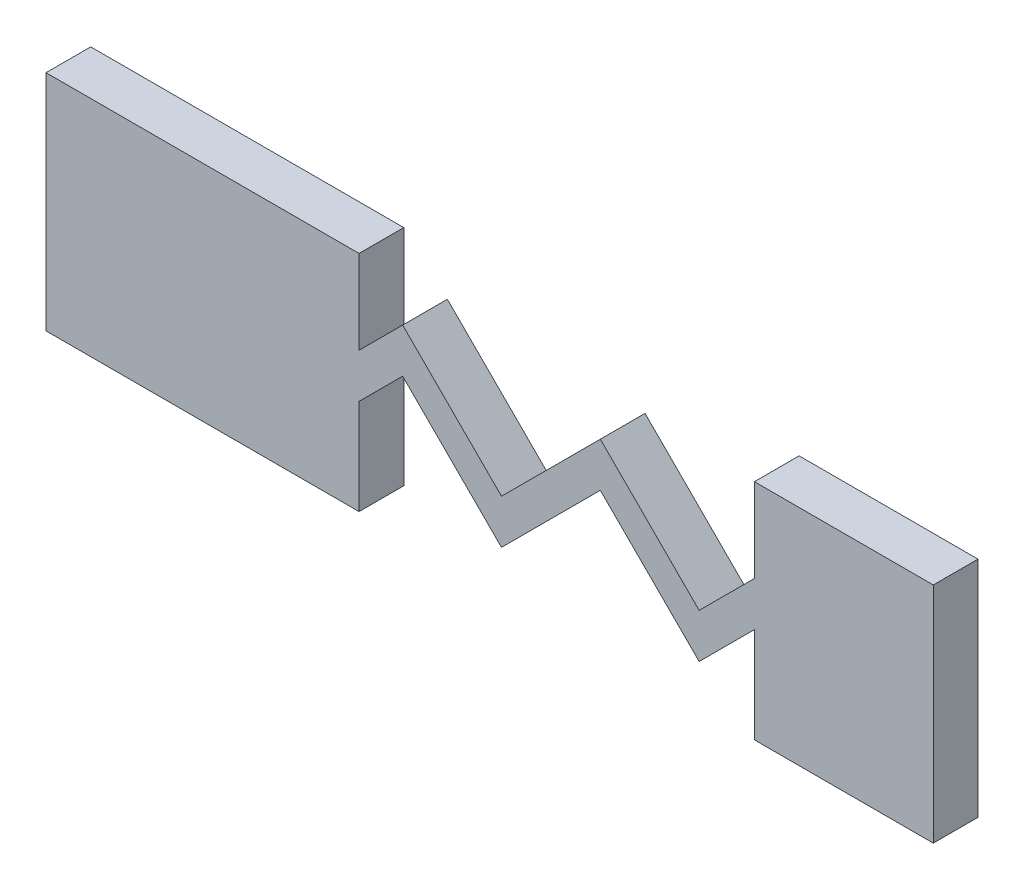
SolidWorks part; units mm, degrees
ref_plane "Front Plane" through (0, 0, 0) normal (0, 0, 1) x (1, 0, 0)
ref_plane "Top Plane" through (0, 0, 0) normal (0, 1, 0) x (1, 0, 0)
ref_plane "Right Plane" through (0, 0, 0) normal (1, 0, 0) x (0, 0, -1)
sketch "Sketch1" plane through (0, 0, 0) normal (0, 0, 1) x (1, 0, 0)
  line L0 (14, 6.25) -> (15.95, 8.2)
  line L1 (0, 0) -> (14, 0)
  line L2 (0, 0) -> (0, 10)
  line L3 (0, 10) -> (14, 10)
  line L4 (14, 0) -> (14, 10)
  line L5 (14, 6.25) -> (14, 4.2701)
  line L6 (15.95, 8.2) -> (15.95, 6.2201)
  line L7 (14, 4.2701) -> (15.95, 6.2201)
  line L9 (15.95, 8.2) -> (15.95, 6.2201)
  line L24 (14, 10) -> (-49986, 10) construction
  line L25 (15.95, 6.2201) -> (20.3701, 1.8)
  line L26 (15.95, 6.2201) -> (15.95, 8.2)
  line L31 (20.3701, 1.8) -> (20.3701, 3.7799)
  line L32 (15.95, 8.2) -> (20.3701, 3.7799)
  line L33 (15.95, 8.2) -> (-49984.05, 8.2) construction
  line L34 (20.3701, 1.8) -> (-49979.6299, 1.8) construction
  line L35 (20.3701, 3.7799) -> (15.95, 8.2)
  line L36 (20.3701, 3.7799) -> (20.3701, 1.8)
  line L37 (15.95, 8.2) -> (15.95, 6.2201)
  line L38 (20.3701, 1.8) -> (15.95, 6.2201)
  line L39 (20.3701, 3.7799) -> (24.7902, 8.2)
  line L40 (20.3701, 3.7799) -> (20.3701, 1.8)
  line L41 (24.7902, 8.2) -> (24.7902, 6.2201)
  line L42 (20.3701, 1.8) -> (24.7902, 6.2201)
  line L43 (24.7902, 6.2201) -> (29.2103, 1.8)
  line L44 (24.7902, 6.2201) -> (24.7902, 8.2)
  line L45 (29.2103, 1.8) -> (29.2103, 3.7799)
  line L46 (24.7902, 8.2) -> (29.2103, 3.7799)
  line L47 (29.2103, 3.7799) -> (31.6804, 6.25)
  line L48 (29.2103, 3.7799) -> (29.2103, 1.8)
  line L49 (31.6804, 6.25) -> (31.6804, 4.2701)
  line L50 (29.2103, 1.8) -> (31.6804, 4.2701)
  line L51 (14, 6.25) -> (-49986, 6.25) construction
  line L52 (14, 10) -> (-49986, 10) construction
  line L53 (14.8952, 0) -> (-49985.1048, 0) construction
  line L54 (31.6804, 6.137) -> (31.6804, -49993.863) construction
  line L56 (31.6804, 10) -> (39.6804, 10)
  line L57 (31.6804, 10) -> (31.6804, 0)
  line L58 (31.6804, 0) -> (39.6804, 0)
  line L59 (39.6804, 10) -> (39.6804, 0)
  dimension "D1" = 10
  dimension "D2" = 14
  dimension "D3" = 45
  dimension "D4" = 3.75
  dimension "D5" = 1.8
  dimension "D6" = 1.8
  dimension "D7" = 1.4
  dimension "D8" = 90
  dimension "D9" = 1.4
  dimension "D10" = 1.4
  dimension "D11" = 1.4
  dimension "D12" = 1.4
  dimension "D13" = 8
extrude "Boss-Extrude1" add sketch "Sketch1" along normal blind 2 contours L1 L4 L3 L2 | L4 L7 L6 L0 | L6 L32 | L32 L38 | L44 L42 | L46 L41 L43 L45 | L45 L50 L49 L47 | L59 L56 L57 L49 L58 | L43 L44 L46 L45 | L47 L48 L50 L49 | L57 L56 L59 L58 region at (14.975, 6.2351, 0) region at (7, 5, 0) region at (18.1601, 5, 0) region at (22.5802, 5, 0) region at (27.0003, 5, 0) region at (30.4454, 4.025, 0) region at (35.6804, 5, 0)
